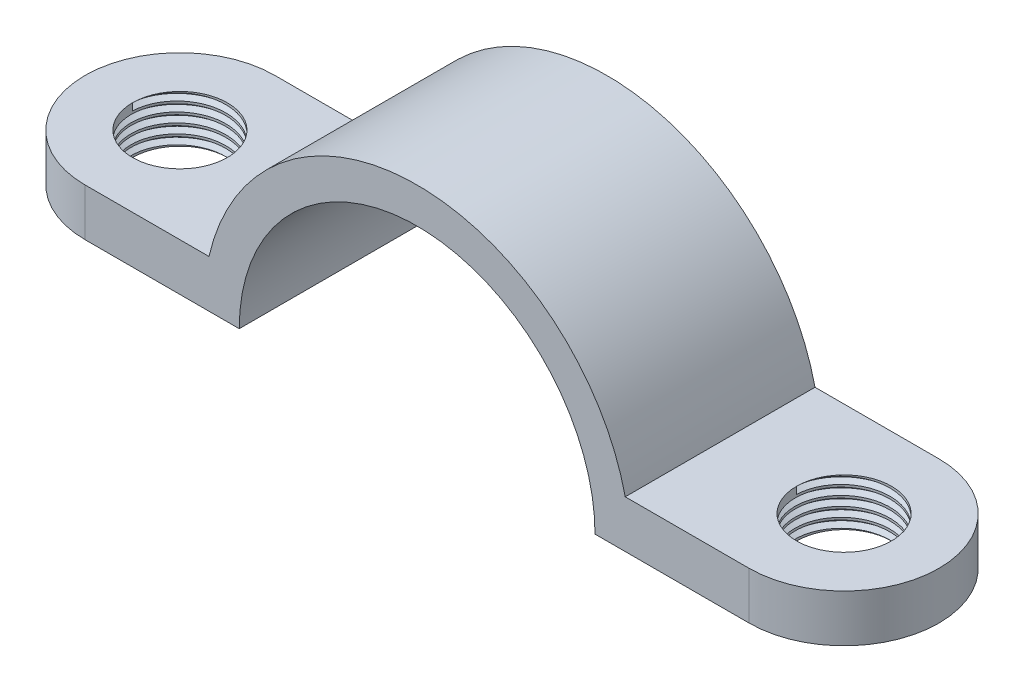
SolidWorks part; units mm, degrees
material "Brass"
ref_plane "Front Plane" through (0, 0, 0) normal (0, 0, 1) x (1, 0, 0)
ref_plane "Top Plane" through (0, 0, 0) normal (0, 1, 0) x (1, 0, 0)
ref_plane "Right Plane" through (0, 0, 0) normal (1, 0, 0) x (0, 0, -1)
sketch "Sketch2" plane through (0, 0, 0) normal (0, 0, 1) x (1, 0, 0)
  circle A0 centre (0, 0) radius 7.5
  circle A1 centre (0, 0) radius 9
  dimension "D1" = 15
  dimension "D2" = 18
extrude "Boss-Extrude1" add sketch "Sketch2" along normal mid plane 8
sketch "Sketch3" plane through (0, 0, 0) normal (0, 1, 0) x (1, 0, 0)
  line L0 (9, 4) -> (14, 4)
  line L1 (9, -4) -> (14, -4)
  line L2 (9, -4) -> (9, 4) construction
  line L3 (9, 4) -> (7.5, 4)
  line L4 (9, 4) -> (-9, 4) construction
  line L5 (7.5, 4) -> (-7.5, 4) construction
  line L6 (7.5, 4) -> (7.5, -4)
  line L7 (7.5, -4) -> (9, -4)
  arc A0 (14, 4) -> (14, -4) centre (14, 0) cw
  circle A1 centre (14, 0) radius 2
  dimension "D2" = 4
  dimension "D1" = 5
extrude "Boss-Extrude2" add sketch "Sketch3" along normal blind 2 contours A0 L0 L3 L6 L7 L1 A1 region at (11.5, 0, -3.868)
mirror "Mirror1" about plane through (0, 0, 0) normal (1, 0, 0) of "Boss-Extrude2", "Boss-Extrude1"
sketch "Sketch4" plane through (0, 0, 0) normal (0, 0, 1) x (1, 0, 0)
  line L0 (4.4, 0) -> (-4.4, 0) construction
  line L1 (-10.3155, 0) -> (19.4076, 0)
  line L2 (-10.3155, 0) -> (-10.3155, -9.5955)
  line L3 (-10.3155, -9.5955) -> (19.4076, -9.5955)
  line L4 (19.4076, 0) -> (19.4076, -9.5955)
extrude "Cut-Extrude2" cut sketch "Sketch4" against normal mid plane 10
ref_plane "Plane4" through (0, 6, 0) normal (0, 1, 0) x (1, 0, 0)
thread "Thread2" pitch 0.4 method cut profile "Thread Profile2" start angle 0, offset 0, length 8, pitch 0.4, diameter 4
ref_plane "Plane6" through (-16, 2, 0) normal (0, 0, 1) x (-1, 0, 0)
sketch "Thread Profile2" plane through (-16, 2, 0) normal (0, 0, 1) x (-1, 0, 0)
  line L0 (0, 0) -> (0, 0.4) construction
  line L1 (0, 0) -> (0.2165, 0.125)
  line L2 (0.2165, 0.125) -> (0.2165, 0.175)
  line L3 (0.2165, 0.175) -> (0, 0.3)
  line L4 (0.2165, 0.15) -> (0, 0.15) construction
  line L11 (0, 0) -> (0, 0.3)
  point P2 (0, 0)
  dimension "Pitch" = 0.4
  dimension "Profile_Angle" = 60
  dimension "Profile_Land" = 0.05
  dimension "Profile_Height" = 0.2165
thread "Thread3" pitch 0.4 method cut profile "Thread Profile3" start angle 0, offset 0, length 8, pitch 0.4, diameter 4
ref_plane "Plane7" through (12, 2, 0) normal (0, 0, 1) x (-1, 0, 0)
sketch "Thread Profile3" plane through (12, 2, 0) normal (0, 0, 1) x (-1, 0, 0)
  line L0 (0, 0) -> (0, 0.4) construction
  line L1 (0, 0) -> (0.2165, 0.125)
  line L2 (0.2165, 0.125) -> (0.2165, 0.175)
  line L3 (0.2165, 0.175) -> (0, 0.3)
  line L4 (0.2165, 0.15) -> (0, 0.15) construction
  line L11 (0, 0) -> (0, 0.3)
  point P2 (0, 0)
  dimension "Pitch" = 0.4
  dimension "Profile_Angle" = 60
  dimension "Profile_Land" = 0.05
  dimension "Profile_Height" = 0.2165
